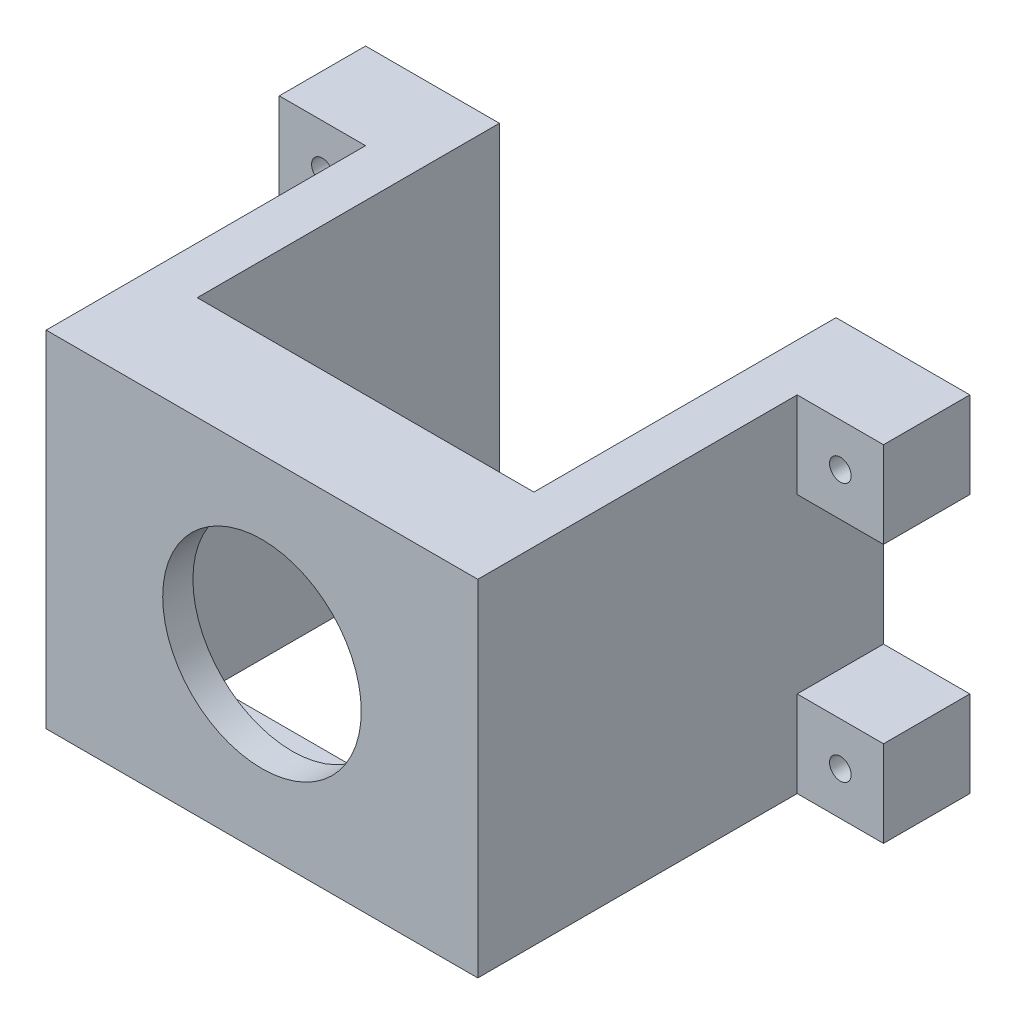
SolidWorks part; units mm, degrees
ref_plane "正面" through (0, 0, 0) normal (0, 0, 1) x (1, 0, 0)
ref_plane "平面" through (0, 0, 0) normal (0, 1, 0) x (1, 0, 0)
ref_plane "右側面" through (0, 0, 0) normal (1, 0, 0) x (0, 0, -1)
sketch "ｽｹｯﾁ1" plane through (0, 0, 0) normal (0, 0, 1) x (1, 0, 0)
  line L1 (-25, 20) -> (25, 20)
  line L2 (-25, 20) -> (-25, -20)
  line L3 (-25, -20) -> (25, -20)
  line L4 (25, 20) -> (25, -20)
  line L5 (-25, 20) -> (25, -20) construction
  line L6 (-25, -20) -> (25, 20) construction
  point P0 (0, 0)
  dimension "D1" = 40
  dimension "D2" = 50
extrude "ﾎﾞｽ - 押し出し2" add sketch "ｽｹｯﾁ1" along normal blind 47
sketch "ｽｹｯﾁ3" plane through (0, 0, 0) normal (0, 0, 1) x (1, 0, 0)
  line L0 (-25, -20) -> (25, -20) construction
  line L1 (-35, -10) -> (35, -10)
  line L2 (-35, -10) -> (-35, -20)
  line L3 (-35, -20) -> (35, -20)
  line L4 (35, -10) -> (35, -20)
  line L5 (-35, -10) -> (35, -20) construction
  line L6 (-35, -20) -> (35, -10) construction
  point P0 (0, -15)
  dimension "D1" = 70
  dimension "D2" = 0
  dimension "D3" = 10
  dimension "D4" = 0
extrude "ﾎﾞｽ - 押し出し3" add sketch "ｽｹｯﾁ3" along normal blind 10
sketch "ｽｹｯﾁ4" plane through (0, 0, 0) normal (0, 0, 1) x (1, 0, 0)
  circle A0 centre (0, 0) radius 11.5
  dimension "D1" = 23
extrude "ｶｯﾄ - 押し出し1" cut sketch "ｽｹｯﾁ4" along normal through all both and the other way through all contours A0
sketch "ｽｹｯﾁ5" plane through (0, 0, 0) normal (0, 0, 1) x (1, 0, 0)
  line L1 (-19.5, 18) -> (19.5, 18)
  line L2 (-19.5, 18) -> (-19.5, -18)
  line L3 (-19.5, -18) -> (19.5, -18)
  line L4 (19.5, 18) -> (19.5, -18)
  line L5 (-19.5, 18) -> (19.5, -18) construction
  line L6 (-19.5, -18) -> (19.5, 18) construction
  point P0 (0, 0)
  dimension "D1" = 39
  dimension "D2" = 36
extrude "ｶｯﾄ - 押し出し2" cut sketch "ｽｹｯﾁ5" along normal blind 43.5
hole_wizard "M3x0.5 ねじ穴1" positions "ｽｹｯﾁ6" profile "ｽｹｯﾁ7" tap size "M3x0.5" standard "JIS" end condition through all
sketch "ｽｹｯﾁ6" plane through (0, 0, 10) normal (0, 0, 1) x (1, 0, 0)
  point P0 (30, -15)
  point P2 (-30, -15)
  dimension "D1" = 30
  dimension "D2" = 30
  dimension "D3" = 15
  dimension "D4" = 15
sketch "ｽｹｯﾁ7" plane through (30, -15, 10) normal (1, 0, 0) x (0, -1, 0)
  line L0 (0, 0) -> (0, 10)
  line L1 (0, 10) -> (1.25, 10)
  line L2 (1.25, 10) -> (1.25, 0)
  line L5 (1.25, 0) -> (0, 0)
  line L11 (0, -6.35) -> (0, 107.95) construction
  dimension "次ｻｰﾌｪｽまでのねじ下穴ﾄﾞﾘﾙ直径" = 2.5
  dimension "次ｻｰﾌｪｽまでのねじ下穴ﾄﾞﾘﾙの深さ" = 10
cosmetic thread "穴のねじ山1" parameters "D2"=3
cosmetic thread "穴のねじ山2" parameters "D2"=3
sketch "ｽｹｯﾁ8" plane through (0, 0, 0) normal (0, 0, -1) x (-1, 0, 0)
  line L1 (-19.5, 35) -> (19.5, 35)
  line L2 (-19.5, 35) -> (-19.5, -35)
  line L3 (-19.5, -35) -> (19.5, -35)
  line L4 (19.5, 35) -> (19.5, -35)
  line L5 (-19.5, 35) -> (19.5, -35) construction
  line L6 (-19.5, -35) -> (19.5, 35) construction
  point P0 (0, 0)
  dimension "D1" = 39
  dimension "D2" = 70
extrude "ｶｯﾄ - 押し出し3" cut sketch "ｽｹｯﾁ8" against normal blind 35
mirror "ﾐﾗｰ4" about plane through (0, 0, 0) normal (0, 1, 0) of "ｶｯﾄ - 押し出し2", "ｶｯﾄ - 押し出し3", "M3x0.5 ねじ穴1", "ﾎﾞｽ - 押し出し3"
cosmetic thread "穴のねじ山7" parameters "D2"=3
cosmetic thread "穴のねじ山8" parameters "D2"=3
